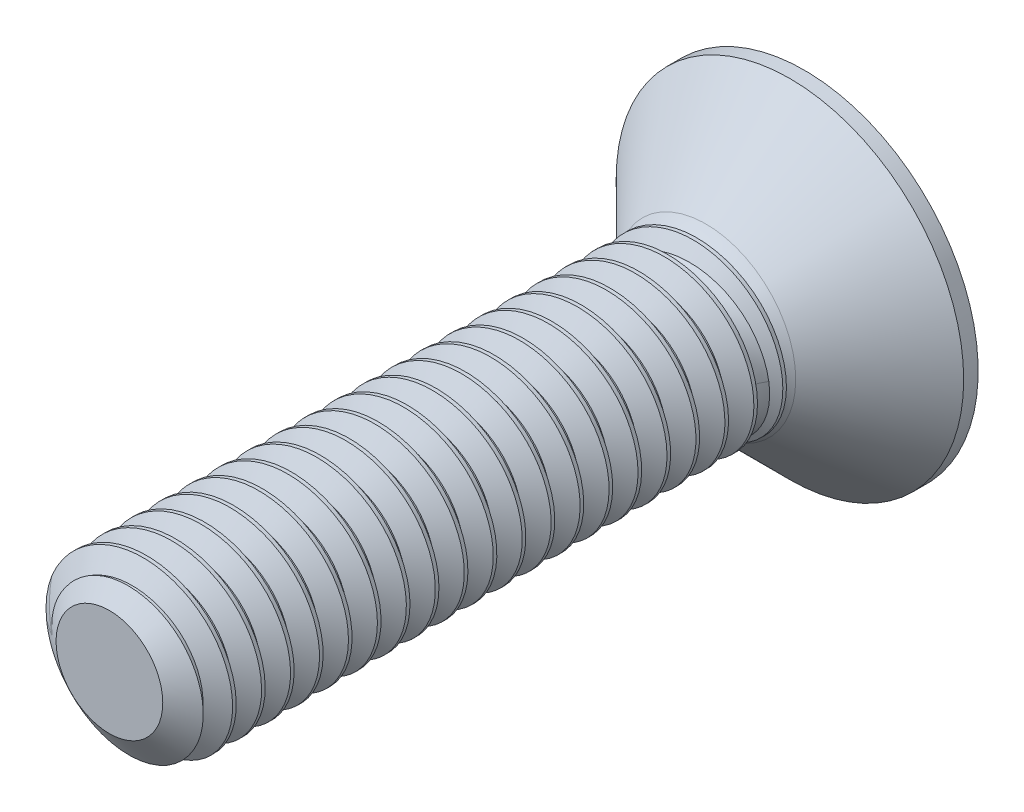
SolidWorks part; units mm, degrees
ref_plane "Front Plane" through (0, 0, 0) normal (0, 0, 1) x (1, 0, 0)
ref_plane "Top Plane" through (0, 0, 0) normal (0, 1, 0) x (1, 0, 0)
ref_plane "Right Plane" through (0, 0, 0) normal (1, 0, 0) x (0, 0, -1)
sketch "Sketch1" plane through (0, 0, 0) normal (0, 0, 1) x (1, 0, 0)
  circle A0 centre (0, 0) radius 1.5
  dimension "OD" = 3
extrude "Extrude1" add sketch "Sketch1" against normal blind 12
sketch "Sketch2" plane through (0, 0, 0) normal (0, 0, 1) x (1, 0, 0)
  circle A0 centre (0, 0) radius 1.5 construction
  circle A1 centre (0, 0) radius 1.5
curve "Helix/Spiral1" pitch 0.5 height 12.5 turns 25 parameters "pitch"=0.5
sketch "Sketch3" plane through (0, 0, 0) normal (1, 0, 0) x (0, 0, -1)
  line L0 (-0.4375, 1.5) -> (-0.25, 1.1752)
  line L1 (-0.25, 1.1752) -> (-0.1875, 1.1752)
  line L2 (-0.1875, 1.1752) -> (0, 1.5)
  line L3 (-0.4375, 1.5) -> (0, 1.5)
  line L4 (-0.2188, 1.5) -> (-0.2188, 1.1752) construction
  line L5 (-0.3438, 1.3376) -> (-0.0937, 1.3376) construction
  line L6 (0, 1.5) -> (0, -1.5) construction
  dimension "D1" = 0.0625
  dimension "D2" = 0.25
  dimension "D3" = 60
sweep "Cut-Sweep1" cut profiles "Sketch3" path "Helix/Spiral1"
sketch "Sketch4" plane through (0, 0, 0) normal (1, 0, 0) x (0, 0, -1)
  line L0 (0.4053, 1.5) -> (0, 0.9212)
  line L1 (0, 0.9212) -> (0, 1.5)
  line L2 (0.4053, 1.5) -> (0, 1.5)
  line L3 (-0.4375, 1.5) -> (0, 1.5) construction
  line L4 (0, 0) -> (7.0209, 0) construction
  dimension "D1" = 55
  dimension "D2" = 0.254
revolve "Cut-Revolve1" cut sketch "Sketch4" angle 360 about L4
sketch "Sketch5" plane through (0, 0, 0) normal (1, 0, 0) x (0, 0, -1)
  line L0 (12, -1.1822) -> (12, 1.0703) construction
  line L1 (12, 1.55) -> (18.1906, 1.55)
  line L2 (12, 1.55) -> (12, 0)
  line L3 (12, 0) -> (18, 0)
  line L4 (18, 1.2198) -> (18, 0)
  line L5 (18.1906, 1.55) -> (18, 1.2198)
  line L6 (0, 0) -> (9.9695, 0) construction
  point P3 (18, 1.55)
  point P10 (18, 1.55)
  dimension "D1" = 0.3302
  dimension "Thread min" = 18
  dimension "D2" = 0.05
  dimension "D3" = 30
revolve "partially thread" [suppressed] add sketch "Sketch5" angle 360 about L6
sketch "Sketch6" plane through (0, 0, -12) normal (0, 0, -1) x (-1, 0, 0)
  circle A0 centre (0, 0) radius 3
  dimension "head dia" = 6
extrude "Extrude2" add sketch "Sketch6" against normal blind 1.7
sketch "Sketch10" plane through (0, 0, 0) normal (1, 0, 0) x (0, 0, -1)
  line L0 (11.75, -3) -> (10.3, -1.55)
  line L1 (10.3, -1.55) -> (10.3, -3)
  line L2 (11.75, -3) -> (10.3, -3)
  line L3 (0, 0) -> (10.3, 0) construction
  line L4 (10.3, 3) -> (10.3, -3) construction
  line L5 (11.75, 3) -> (10.3, 3) construction
  line L6 (10.3, 1.55) -> (10.3, 3) construction
  line L7 (11.75, 3) -> (10.3, 1.55) construction
  line L8 (10.3, 3) -> (10.3, -3) construction
  line L9 (10.3, 1.55) -> (10.3, -1.55) construction
  dimension "D1" = 45
  dimension "D2" = 0.05
revolve "Cut-Revolve2" cut sketch "Sketch10" angle 360 about L3
sketch "Sketch11" plane through (0, 0, 0) normal (1, 0, 0) x (0, 0, -1)
  line L0 (-0.25, 1.1752) -> (-0.1875, 1.1752) construction
  line L1 (11.75, 3) -> (10.3, 1.55) construction
  line L2 (9.3953, 1.1752) -> (9.3953, 0)
  line L3 (9.3953, 0) -> (10.3, 0)
  line L4 (10.3, 1.55) -> (10.3, 0)
  line L5 (0, 0) -> (10.3, 0) construction
  arc A0 (10.3, 1.55) -> (9.3953, 1.1752) centre (9.3953, 2.4547) cw
revolve "Revolve1" add sketch "Sketch11" angle 360 about L3
sketch "Sketch7" plane through (0, 0, -12) normal (0, 0, 1) x (1, 0, 0)
  line L1 (0, 1.1547) -> (-1, 0.5774)
  line L2 (-1, 0.5774) -> (-1, -0.5774)
  line L3 (-1, -0.5774) -> (0, -1.1547)
  line L4 (0, -1.1547) -> (1, -0.5774)
  line L5 (1, -0.5774) -> (1, 0.5774)
  line L6 (1, 0.5774) -> (0, 1.1547)
  circle A0 centre (0, 0) radius 1 construction
  dimension "hex dia" = 2
extrude "Cut-Extrude1" cut sketch "Sketch7" along normal blind 1.5
sketch "Sketch8" plane through (0, 0, -12) normal (0, 0, 1) x (1, 0, 0)
  circle A0 centre (0, 0) radius 1.1547
extrude "Cut-Extrude2" cut sketch "Sketch8" along normal through all draft 45
sketch "Sketch9" plane through (0, 0, 0) normal (1, 0, 0) x (0, 0, -1)
  line L0 (0, 1.5) -> (0, -1.5) construction
  line L1 (2.75, 1.5) -> (2.75, -1.5) construction
  line L2 (10.3, 1.5) -> (10.3, -1.5) construction
  line L3 (10.3, -1.55) -> (10.3, -3) construction
  dimension "D1" = 2.75
equation "\"D3@Helix/Spiral1\" = \"screw length@Extrude1\"+\"pitch@Helix/Spiral1\""
equation "\"D1@Sketch3\" = \"pitch@Helix/Spiral1\"*.125"
equation "\"D2@Sketch3\" = \"pitch@Helix/Spiral1\"*.5"
equation "\"D1@Cut-Extrude1\" = \"hex dia@Sketch7\"*.75"
equation "\"D1@Sketch9\" = \"pitch@Helix/Spiral1\"*5.5"
equation "\"D2@Sketch10\" = \"D2@Sketch5\""
